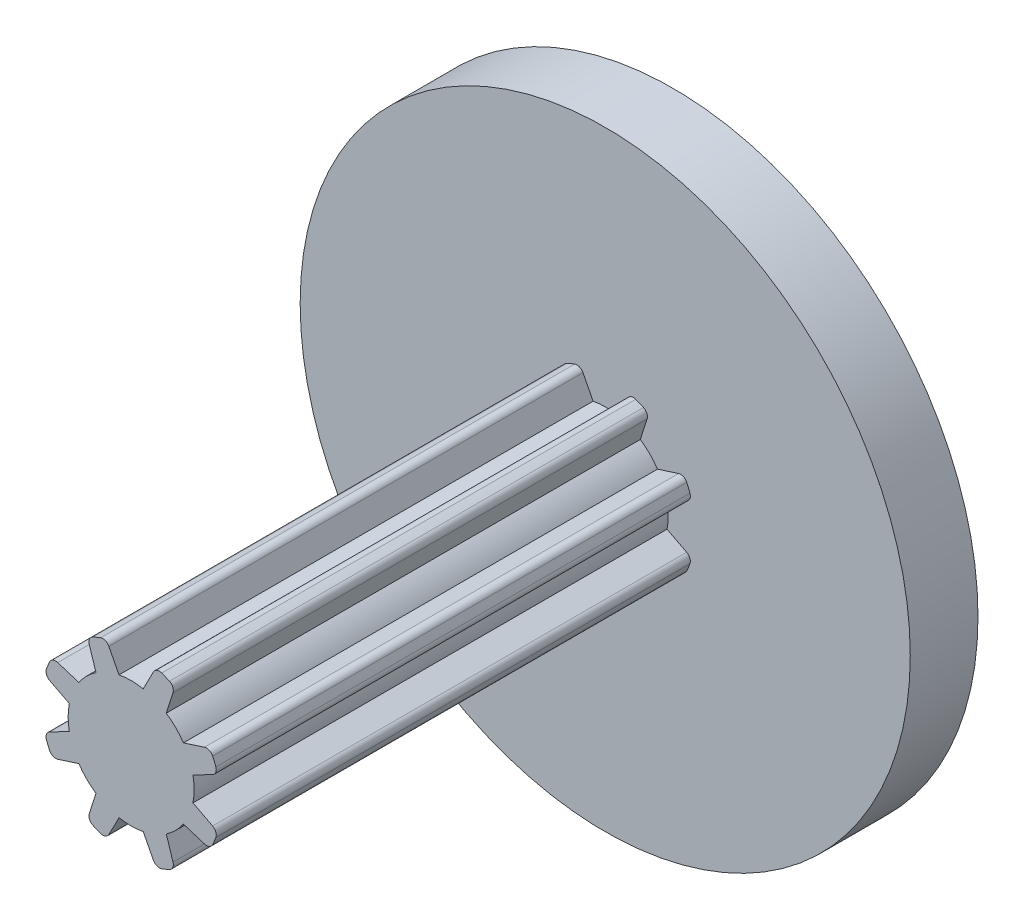
SolidWorks part; units mm, degrees
note: The reader was unsure of these and kept them because the rebuilt part matched: shared geometry of "Sketch2<4>".
ref_plane "Front Plane" through (0, 0, 0) normal (0, 0, 1) x (1, 0, 0)
ref_plane "Top Plane" through (0, 0, 0) normal (0, 1, 0) x (1, 0, 0)
ref_plane "Right Plane" through (0, 0, 0) normal (1, 0, 0) x (0, 0, -1)
sketch "Sketch2" plane through (0, 0, -16.4539) normal (0, 0, 1) x (1, 0, 0)
  line L0 (0, 4.65) -> (0, -4.65) construction
  line L3 (-4.65, 0) -> (4.65, 0) construction
  line L18 (-2.5947, 3.8588) -> (-2.5451, 6.1437) construction
  line L19 (-2.5451, 6.1437) -> (-0.8938, 4.5633) construction
  line L20 (0, 0) -> (-2.5451, 6.1437) construction
  line L21 (-2.5947, 3.8588) -> (-3.092, 5.4137)
  line L22 (-0.8942, 4.5632) -> (-1.6422, 6.0143)
  line L23 (0.8938, 4.5633) -> (1.6417, 6.0144)
  line L24 (2.5944, 3.859) -> (3.0915, 5.414)
  line L25 (3.8588, 2.5947) -> (5.4137, 3.092)
  line L26 (4.5632, 0.8942) -> (6.0143, 1.6422)
  line L27 (4.5633, -0.8938) -> (6.0144, -1.6417)
  line L28 (3.859, -2.5944) -> (5.414, -3.0915)
  line L29 (2.5947, -3.8588) -> (3.092, -5.4137)
  line L30 (0.8942, -4.5632) -> (1.6422, -6.0143)
  line L31 (-0.8938, -4.5633) -> (-1.6417, -6.0144)
  line L32 (-2.5944, -3.859) -> (-3.0915, -5.414)
  line L33 (-3.8588, -2.5947) -> (-5.4137, -3.092)
  line L34 (-4.5632, -0.8942) -> (-6.0143, -1.6422)
  line L35 (-4.5633, 0.8938) -> (-6.0144, 1.6417)
  line L36 (-3.859, 2.5944) -> (-5.414, 3.0915)
  circle A0 centre (0, 0) radius 4.1371
  circle A1 centre (0, 0) radius 22.5218
  arc A2 (-2.5947, 3.8588) -> (-3.859, 2.5944) centre (0, 0) ccw
  arc A3 (-6.0188, 2.8279) -> (-6.2557, 2.2558) centre (0, 0) ccw
  arc A4 (-6.2555, -2.2563) -> (-6.0185, -2.8284) centre (0, 0) ccw
  arc A5 (-2.8279, -6.0188) -> (-2.2558, -6.2557) centre (0, 0) ccw
  arc A6 (2.2563, -6.2555) -> (2.8284, -6.0185) centre (0, 0) ccw
  arc A7 (6.0188, -2.8279) -> (6.2557, -2.2558) centre (0, 0) ccw
  arc A8 (6.2555, 2.2563) -> (6.0185, 2.8284) centre (0, 0) ccw
  arc A9 (2.8279, 6.0188) -> (2.2558, 6.2557) centre (0, 0) ccw
  arc A10 (-2.2563, 6.2555) -> (-2.8284, 6.0185) centre (0, 0) ccw
  arc A11 (0.8938, 4.5633) -> (-0.8942, 4.5632) centre (0, 0) ccw
  arc A12 (3.8588, 2.5947) -> (2.5944, 3.859) centre (0, 0) ccw
  arc A13 (4.5633, -0.8938) -> (4.5632, 0.8942) centre (0, 0) ccw
  arc A14 (2.5947, -3.8588) -> (3.859, -2.5944) centre (0, 0) ccw
  arc A15 (-0.8938, -4.5633) -> (0.8942, -4.5632) centre (0, 0) ccw
  arc A16 (-3.8588, -2.5947) -> (-2.5944, -3.859) centre (0, 0) ccw
  arc A17 (-4.5633, 0.8938) -> (-4.5632, -0.8942) centre (0, 0) ccw
  arc A18 (-5.414, 3.0915) -> (-6.0188, 2.8279) centre (-5.5662, 2.6153) ccw
  arc A19 (-6.0144, 1.6417) -> (-6.2557, 2.2558) centre (-5.7854, 2.0862) cw
  arc A20 (-6.0143, -1.6422) -> (-6.2555, -2.2563) centre (-5.7852, -2.0866) ccw
  arc A21 (-5.4137, -3.092) -> (-6.0185, -2.8284) centre (-5.566, -2.6157) cw
  arc A22 (-3.0915, -5.414) -> (-2.8279, -6.0188) centre (-2.6153, -5.5662) ccw
  arc A23 (-1.6417, -6.0144) -> (-2.2558, -6.2557) centre (-2.0862, -5.7854) cw
  arc A24 (1.6422, -6.0143) -> (2.2563, -6.2555) centre (2.0866, -5.7852) ccw
  arc A25 (3.092, -5.4137) -> (2.8284, -6.0185) centre (2.6157, -5.566) cw
  arc A26 (5.414, -3.0915) -> (6.0188, -2.8279) centre (5.5662, -2.6153) ccw
  arc A27 (6.0144, -1.6417) -> (6.2557, -2.2558) centre (5.7854, -2.0862) cw
  arc A28 (6.0143, 1.6422) -> (6.2555, 2.2563) centre (5.7852, 2.0866) ccw
  arc A29 (5.4137, 3.092) -> (6.0185, 2.8284) centre (5.566, 2.6157) cw
  arc A30 (3.0915, 5.414) -> (2.8279, 6.0188) centre (2.6153, 5.5662) ccw
  arc A31 (1.6417, 6.0144) -> (2.2558, 6.2557) centre (2.0862, 5.7854) cw
  arc A32 (-1.6422, 6.0143) -> (-2.2563, 6.2555) centre (-2.0866, 5.7852) ccw
  arc A33 (-3.092, 5.4137) -> (-2.8284, 6.0185) centre (-2.6157, 5.566) cw
  point P45 (0, 0)
  point P71 (-1.8366, 6.3914)
  point P76 (-3.2212, 5.8178)
  point P77 (0, 0)
  dimension "D1" = 9.3
  dimension "D2" = 13.3
  dimension "D3" = 0.5
  dimension "D4" = 8.2743
  dimension "D5" = 8
extrude "Boss-Extrude1" add sketch "Sketch2" along normal blind 40 contours A2 A0
extrude "Boss-Extrude2" add sketch "Sketch2<4>" along normal blind 5 contours A1
sketch "Sketch2<4>" plane through (0, 0, -16.4539) normal (0, 0, 1) x (1, 0, 0) same geometry as "Sketch2"
sketch "Sketch3" plane through (0, 0, -16.4539) normal (0, 0, -1) x (-1, 0, 0)
  circle A0 centre (0, 0) radius 3.05
  dimension "D1" = 6.1
sketch "Sketch5" plane through (0, 0, -11.4539) normal (0, 0, 1) x (1, 0, 0)
  line L0 (3.0915, 5.414) -> (2.5944, 3.859)
  line L1 (0.8938, 4.5633) -> (1.6417, 6.0144)
  line L2 (6.0143, 1.6422) -> (4.5632, 0.8942)
  line L3 (3.8588, 2.5947) -> (5.4137, 3.092)
  line L4 (-1.6422, 6.0143) -> (-0.8942, 4.5632)
  line L5 (-2.5947, 3.8588) -> (-3.092, 5.4137)
  line L6 (-1.6422, 6.0143) -> (-0.8942, 4.5632)
  line L7 (-2.5947, 3.8588) -> (-3.092, 5.4137)
  line L8 (5.414, -3.0915) -> (3.859, -2.5944)
  line L9 (4.5633, -0.8938) -> (6.0144, -1.6417)
  line L10 (1.6422, -6.0143) -> (0.8942, -4.5632)
  line L11 (2.5947, -3.8588) -> (3.092, -5.4137)
  line L12 (-3.0915, -5.414) -> (-2.5944, -3.859)
  line L13 (-0.8938, -4.5633) -> (-1.6417, -6.0144)
  line L14 (-6.0143, -1.6422) -> (-4.5632, -0.8942)
  line L15 (-3.8588, -2.5947) -> (-5.4137, -3.092)
  line L16 (-5.414, 3.0915) -> (-3.859, 2.5944)
  line L17 (-4.5633, 0.8938) -> (-6.0144, 1.6417)
  arc A0 (3.8588, 2.5947) -> (2.5944, 3.859) centre (0, 0) ccw
  arc A1 (3.0915, 5.414) -> (2.8279, 6.0188) centre (2.6153, 5.5662) ccw
  arc A2 (2.8279, 6.0188) -> (2.2558, 6.2557) centre (0, 0) ccw
  arc A3 (2.2558, 6.2557) -> (1.6417, 6.0144) centre (2.0862, 5.7854) ccw
  arc A4 (4.5633, -0.8938) -> (4.5632, 0.8942) centre (0, 0) ccw
  arc A5 (6.0143, 1.6422) -> (6.2555, 2.2563) centre (5.7852, 2.0866) ccw
  arc A6 (6.2555, 2.2563) -> (6.0185, 2.8284) centre (0, 0) ccw
  arc A7 (6.0185, 2.8284) -> (5.4137, 3.092) centre (5.566, 2.6157) ccw
  arc A8 (2.5947, -3.8588) -> (3.859, -2.5944) centre (0, 0) ccw
  arc A9 (0.8938, 4.5633) -> (-0.8942, 4.5632) centre (0, 0) ccw
  arc A10 (-1.6422, 6.0143) -> (-2.2563, 6.2555) centre (-2.0866, 5.7852) ccw
  arc A11 (-2.2563, 6.2555) -> (-2.8284, 6.0185) centre (0, 0) ccw
  arc A12 (-2.8284, 6.0185) -> (-3.092, 5.4137) centre (-2.6157, 5.566) ccw
  arc A13 (0.8938, 4.5633) -> (-0.8942, 4.5632) centre (0, 0) ccw
  arc A14 (-1.6422, 6.0143) -> (-2.2563, 6.2555) centre (-2.0866, 5.7852) ccw
  arc A15 (-2.2563, 6.2555) -> (-2.8284, 6.0185) centre (0, 0) ccw
  arc A16 (-2.8284, 6.0185) -> (-3.092, 5.4137) centre (-2.6157, 5.566) ccw
  arc A17 (5.414, -3.0915) -> (6.0188, -2.8279) centre (5.5662, -2.6153) ccw
  arc A18 (6.0188, -2.8279) -> (6.2557, -2.2558) centre (0, 0) ccw
  arc A19 (6.2557, -2.2558) -> (6.0144, -1.6417) centre (5.7854, -2.0862) ccw
  arc A20 (-0.8938, -4.5633) -> (0.8942, -4.5632) centre (0, 0) ccw
  arc A21 (1.6422, -6.0143) -> (2.2563, -6.2555) centre (2.0866, -5.7852) ccw
  arc A22 (2.2563, -6.2555) -> (2.8284, -6.0185) centre (0, 0) ccw
  arc A23 (2.8284, -6.0185) -> (3.092, -5.4137) centre (2.6157, -5.566) ccw
  arc A24 (-3.8588, -2.5947) -> (-2.5944, -3.859) centre (0, 0) ccw
  arc A25 (-3.0915, -5.414) -> (-2.8279, -6.0188) centre (-2.6153, -5.5662) ccw
  arc A26 (-2.8279, -6.0188) -> (-2.2558, -6.2557) centre (0, 0) ccw
  arc A27 (-2.2558, -6.2557) -> (-1.6417, -6.0144) centre (-2.0862, -5.7854) ccw
  arc A28 (-4.5633, 0.8938) -> (-4.5632, -0.8942) centre (0, 0) ccw
  arc A29 (-6.0143, -1.6422) -> (-6.2555, -2.2563) centre (-5.7852, -2.0866) ccw
  arc A30 (-6.2555, -2.2563) -> (-6.0185, -2.8284) centre (0, 0) ccw
  arc A31 (-6.0185, -2.8284) -> (-5.4137, -3.092) centre (-5.566, -2.6157) ccw
  arc A32 (-2.5947, 3.8588) -> (-3.859, 2.5944) centre (0, 0) ccw
  arc A33 (-5.414, 3.0915) -> (-6.0188, 2.8279) centre (-5.5662, 2.6153) ccw
  arc A34 (-6.0188, 2.8279) -> (-6.2557, 2.2558) centre (0, 0) ccw
  arc A35 (-6.2557, 2.2558) -> (-6.0144, 1.6417) centre (-5.7854, 2.0862) ccw
  point P76 (0, 0)
  dimension "D1" = 0
  dimension "D2" = 8
extrude "Boss-Extrude3" add sketch "Sketch5" along normal blind 35
sketch "Sketch6" plane through (0, 0, -16.4539) normal (0, 0, -1) x (-1, 0, 0)
  circle A0 centre (0, 0) radius 3.1
extrude "Cut-Extrude1" cut sketch "Sketch6" against normal blind 17
